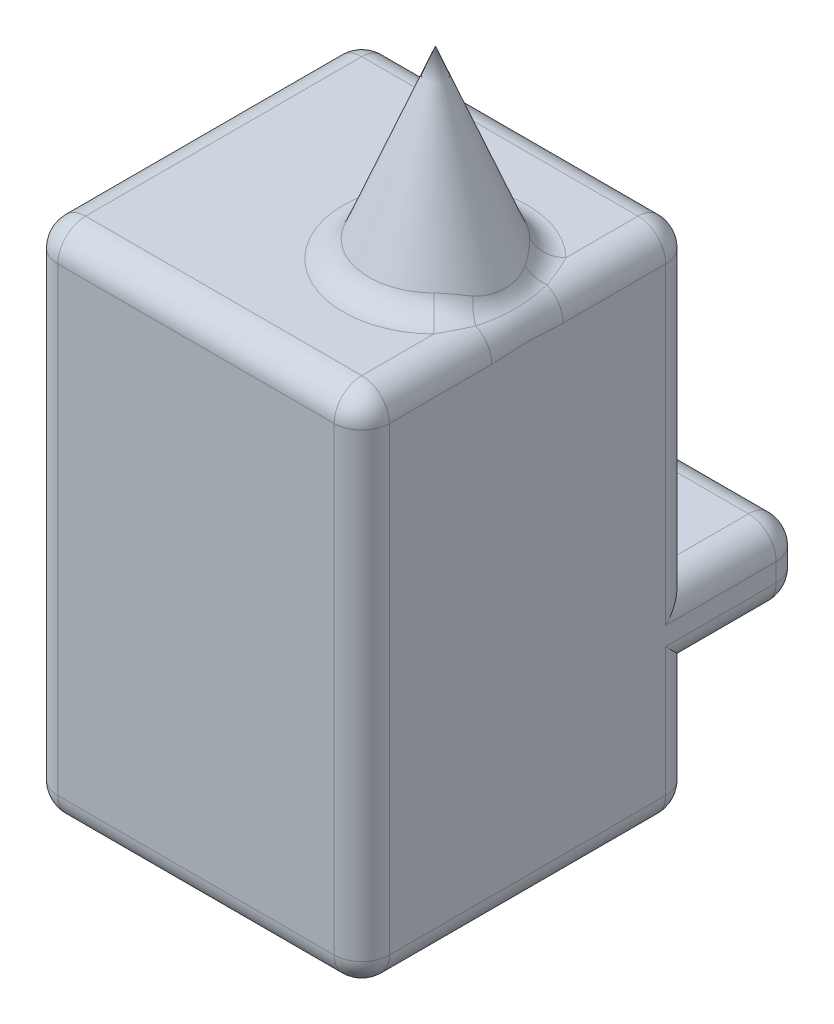
SolidWorks part; units mm, degrees
ref_plane "Front Plane" through (0, 0, 0) normal (0, 0, 1) x (1, 0, 0)
ref_plane "Top Plane" through (0, 0, 0) normal (0, 1, 0) x (1, 0, 0)
ref_plane "Right Plane" through (0, 0, 0) normal (1, 0, 0) x (0, 0, -1)
sketch "Sketch1" plane through (0, 0, 0) normal (0, 1, 0) x (1, 0, 0)
  line L1 (-4.5, -4.5) -> (4.5, -4.5)
  line L2 (-4.5, -4.5) -> (-4.5, 4.5)
  line L3 (-4.5, 4.5) -> (4.5, 4.5)
  line L4 (4.5, -4.5) -> (4.5, 4.5)
  line L5 (-4.5, -4.5) -> (4.5, 4.5) construction
  line L6 (-4.5, 4.5) -> (4.5, -4.5) construction
  point P0 (0, 0)
  dimension "D1" = 9
extrude "Boss-Extrude1" add sketch "Sketch1" along normal blind 14
sketch "Sketch21" plane through (0, 0, -4.5) normal (0, 0, -1) x (-1, 0, 0)
  line L0 (4.5, 14) -> (4.5, 0) construction
  line L1 (4.5, 5.5) -> (-4.5, 5.5)
  line L2 (4.5, 5.5) -> (4.5, 3.5)
  line L3 (4.5, 3.5) -> (-4.5, 3.5)
  line L4 (-4.5, 5.5) -> (-4.5, 3.5)
  line L5 (-4.5, 0) -> (4.5, 0) construction
  line L6 (-4.5, 14) -> (-4.5, 0) construction
  dimension "D2" = 2
  dimension "D3" = 3.5
extrude "Boss-Extrude2" add sketch "Sketch21" along normal blind 3
ref_plane "Plane1" through (0, 1, 0) normal (0, 1, 0) x (1, 0, 0)
ref_plane "Plane2" through (0, 3, 0) normal (0, 1, 0) x (1, 0, 0)
ref_plane "Plane4" through (0, 14, 0) normal (0, -1, 0) x (-1, 0, 0)
ref_plane "Plane5" through (0, 11, 0) normal (0, -1, 0) x (-1, 0, 0)
ref_plane "Plane6" through (0, 13, 0) normal (0, -1, 0) x (-1, 0, 0)
sketch "Sketch13" plane through (4.5, 0, 0) normal (1, 0, 0) x (0, 0, -1)
  line L0 (-4.5, 0) -> (4.5, 0) construction
  line L1 (4.5, 14) -> (4.5, 5.5) construction
  circle A0 centre (0, 4.5) radius 0.625
  dimension "D1" = 1.25
  dimension "D2" = 4.5
  dimension "D3" = 4.5
sketch "Sketch14" plane through (0, 0, 0) normal (0, 0, 1) x (1, 0, 0)
  line L0 (2, 14) -> (2, 7)
  line L3 (4.5, 14) -> (4.5, 0) construction
  line L4 (4.5, 3.875) -> (4.5, 5.125) construction
  arc A0 (2, 7) -> (4.5, 4.5) centre (4.5, 7) ccw
  dimension "D1" = 7
ref_plane "Plane7" through (0, 5.5, 0) normal (0, 1, 0) x (1, 0, 0)
ref_plane "Plane8" through (2, 0, 0) normal (1, 0, 0) x (0, 0, -1)
sketch "Sketch23" plane through (0, 0, 0) normal (0, 0, 1) x (1, 0, 0)
  line L0 (2, 14) -> (2, 19)
  line L1 (2, 19) -> (4, 14)
  line L2 (-4.5, 14) -> (4.5, 14) construction
  line L3 (4, 14) -> (2, 14)
  dimension "D1" = 5
  dimension "D2" = 2
revolve "Revolve1" add sketch "Sketch23" angle 360 about L0
fillet "Fillet1" radius 0.75 22 edges at (0, 14, 4.5) (0, 0, -4.5) (0, 0, 4.5) (4.5, 7, 4.5) (4.5, 14, 0) (4.5, 9.75, -4.5) (4.5, 5.5, -6) (4.5, 4.5, -7.5) (4.5, 3.5, -6) (4.5, 1.75, -4.5) (4.5, 0, 0) (-4.5, 1.75, -4.5) (-4.5, 3.5, -6) (-4.5, 4.5, -7.5) (-4.5, 5.5, -6) (-4.5, 9.75, -4.5) (-4.5, 14, 0) (-4.5, 7, 4.5) (-4.5, 0, 0) (0, 5.5, -7.5) (0, 3.5, -7.5) (0, 14, -4.5)
fillet "Fillet2" radius 0.75 2 edges at (4, 14, 0) (0, 14, 0)
equation "\"bottom_length\"= 9"
equation "\"D1@Sketch1\"= \"bottom_length\""
equation "\"channel_diameter\"=1"
equation "\"D1@Boss-Extrude1\"=\"height\""
equation "\"height\"=14"
equation "\"D1@Sketch14\"=\"height\" - 4.5 - 2.5"
